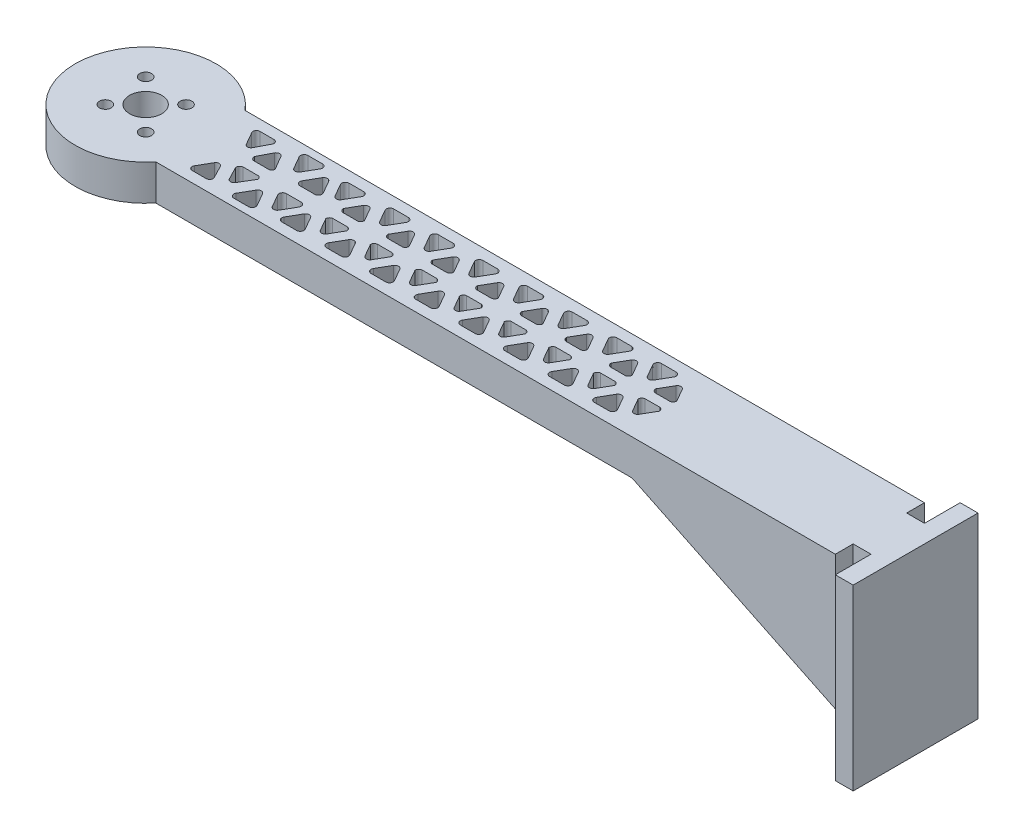
SolidWorks part; units mm, degrees
note: The reader was unsure of these and kept them because the rebuilt part matched: shared geometry of "Sketch2<4>".
ref_plane "Front Plane" through (0, 0, 0) normal (0, 0, 1) x (1, 0, 0)
ref_plane "Top Plane" through (0, 0, 0) normal (0, 1, 0) x (1, 0, 0)
ref_plane "Right Plane" through (0, 0, 0) normal (1, 0, 0) x (0, 0, -1)
sketch "Sketch1" plane through (0, 0, 0) normal (0, 1, 0) x (1, 0, 0)
  line L0 (19.7015, -0.0803) -> (215.7812, -0.0803) construction
  line L1 (15.2517, 12.4197) -> (215.7812, 12.4197)
  line L2 (15.2517, -12.5803) -> (215.7812, -12.5803)
  line L3 (215.7812, 12.4197) -> (215.7812, -12.5803)
  line L4 (22.4549, 9.4197) -> (26.384, 9.4197)
  line L5 (27.2449, 8.0014) -> (25.383, 4.4231)
  line L6 (23.682, 4.3855) -> (21.6147, 7.9638)
  line L7 (29.7182, 6.2554) -> (27.8031, 2.5747)
  line L8 (33.7755, 2.3958) -> (31.5736, 6.0947)
  line L9 (28.7602, 1.4197) -> (33.171, 1.4197)
  line L10 (37.9612, 5.1841) -> (40.0285, 8.7624)
  line L11 (34.1207, 8.7624) -> (36.188, 5.1841)
  line L12 (39.1419, 10.2986) -> (35.0073, 10.2986)
  line L13 (45.3949, 1.819) -> (41.2604, 1.819)
  line L14 (40.3733, 3.3543) -> (42.441, 6.9413)
  line L15 (44.2142, 6.9413) -> (46.2815, 3.363)
  line L16 (47.5213, 9.3393) -> (51.6558, 9.3393)
  line L17 (52.5425, 7.8032) -> (50.4752, 4.2249)
  line L18 (48.702, 4.2249) -> (46.6347, 7.8032)
  line L19 (54.955, 5.982) -> (52.8877, 2.4037)
  line L20 (58.7955, 2.3958) -> (56.7282, 5.982)
  line L21 (53.7743, 1.3393) -> (57.9089, 1.3393)
  line L22 (60.0313, 9.3393) -> (64.1658, 9.3393)
  line L23 (65.0525, 7.8032) -> (62.9852, 4.2249)
  line L24 (61.212, 4.2249) -> (59.1447, 7.8032)
  line L25 (67.465, 5.982) -> (65.3977, 2.4037)
  line L26 (71.3055, 2.3958) -> (69.2382, 5.982)
  line L27 (66.2843, 1.3393) -> (70.4189, 1.3393)
  line L28 (72.5413, 9.3393) -> (76.6758, 9.3393)
  line L29 (77.5625, 7.8032) -> (75.4952, 4.2249)
  line L30 (73.722, 4.2249) -> (71.6547, 7.8032)
  line L31 (79.975, 5.982) -> (77.9077, 2.4037)
  line L32 (83.8155, 2.3958) -> (81.7482, 5.982)
  line L33 (78.7943, 1.3393) -> (82.9289, 1.3393)
  line L34 (85.0513, 9.3393) -> (89.1858, 9.3393)
  line L35 (90.0725, 7.8032) -> (88.0052, 4.2249)
  line L36 (86.232, 4.2249) -> (84.1647, 7.8032)
  line L37 (92.485, 5.982) -> (90.4177, 2.4037)
  line L38 (96.3255, 2.3958) -> (94.2582, 5.982)
  line L39 (91.3043, 1.3393) -> (95.4389, 1.3393)
  line L40 (91.3043, -1.5) -> (95.4389, -1.5)
  line L41 (96.3255, -2.5565) -> (94.2582, -6.1427)
  line L42 (92.485, -6.1427) -> (90.4177, -2.5644)
  line L43 (86.232, -4.3855) -> (84.1647, -7.9638)
  line L44 (90.0725, -7.9638) -> (88.0052, -4.3855)
  line L45 (85.0513, -9.5) -> (89.1858, -9.5)
  line L46 (78.7943, -1.5) -> (82.9289, -1.5)
  line L47 (83.8155, -2.5565) -> (81.7482, -6.1427)
  line L48 (79.975, -6.1427) -> (77.9077, -2.5644)
  line L49 (73.722, -4.3855) -> (71.6547, -7.9638)
  line L50 (77.5625, -7.9638) -> (75.4952, -4.3855)
  line L51 (72.5413, -9.5) -> (76.6758, -9.5)
  line L52 (66.2843, -1.5) -> (70.4189, -1.5)
  line L53 (71.3055, -2.5565) -> (69.2382, -6.1427)
  line L54 (67.465, -6.1427) -> (65.3977, -2.5644)
  line L55 (61.212, -4.3855) -> (59.1447, -7.9638)
  line L56 (65.0525, -7.9638) -> (62.9852, -4.3855)
  line L57 (60.0313, -9.5) -> (64.1658, -9.5)
  line L58 (53.7743, -1.5) -> (57.9089, -1.5)
  line L59 (58.7955, -2.5565) -> (56.7282, -6.1427)
  line L60 (54.955, -6.1427) -> (52.8877, -2.5644)
  line L61 (48.702, -4.3855) -> (46.6347, -7.9638)
  line L62 (52.5425, -7.9638) -> (50.4752, -4.3855)
  line L63 (47.5213, -9.5) -> (51.6558, -9.5)
  line L64 (44.2142, -7.1019) -> (46.2815, -3.5236)
  line L65 (40.3733, -3.5149) -> (42.441, -7.1019)
  line L66 (45.3949, -1.9796) -> (41.2604, -1.9796)
  line L67 (39.1419, -10.4593) -> (35.0073, -10.4593)
  line L68 (34.1207, -8.9231) -> (36.188, -5.3448)
  line L69 (37.9612, -5.3448) -> (40.0285, -8.9231)
  line L70 (28.7602, -1.5803) -> (33.171, -1.5803)
  line L71 (33.7755, -2.5565) -> (31.5736, -6.2554)
  line L72 (29.7182, -6.4161) -> (27.8031, -2.7354)
  line L73 (23.682, -4.5462) -> (21.6147, -8.1245)
  line L74 (27.2449, -8.1621) -> (25.383, -4.5837)
  line L75 (22.4549, -9.5803) -> (26.384, -9.5803)
  line L76 (-0.0803, -16.7095) -> (-0.0803, 16.5488) construction
  line L77 (11.7312, -11.8919) -> (-11.8919, 11.7312) construction
  line L78 (-12.5321, -12.5321) -> (12.3715, 12.3715) construction
  line L79 (97.5613, 9.3393) -> (101.6958, 9.3393)
  line L80 (102.5825, 7.8032) -> (100.5152, 4.2249)
  line L81 (98.742, 4.2249) -> (96.6747, 7.8032)
  line L82 (104.995, 5.982) -> (102.9277, 2.4037)
  line L83 (108.8355, 2.3958) -> (106.7682, 5.982)
  line L84 (103.8143, 1.3393) -> (107.9489, 1.3393)
  line L85 (110.0713, 9.3393) -> (114.2058, 9.3393)
  line L86 (115.0925, 7.8032) -> (113.0252, 4.2249)
  line L87 (111.252, 4.2249) -> (109.1847, 7.8032)
  line L88 (117.505, 5.982) -> (115.4377, 2.4037)
  line L89 (121.3455, 2.3958) -> (119.2782, 5.982)
  line L90 (116.3243, 1.3393) -> (120.4589, 1.3393)
  line L91 (122.5813, 9.3393) -> (126.7158, 9.3393)
  line L92 (127.6025, 7.8032) -> (125.5352, 4.2249)
  line L93 (123.762, 4.2249) -> (121.6947, 7.8032)
  line L94 (130.015, 5.982) -> (127.9477, 2.4037)
  line L95 (133.8555, 2.3958) -> (131.7882, 5.982)
  line L96 (128.8343, 1.3393) -> (132.9689, 1.3393)
  line L97 (135.0913, 9.3393) -> (139.2258, 9.3393)
  line L98 (140.1125, 7.8032) -> (138.0452, 4.2249)
  line L99 (136.272, 4.2249) -> (134.2047, 7.8032)
  line L100 (142.525, 5.982) -> (140.4577, 2.4037)
  line L101 (146.3655, 2.3958) -> (144.2982, 5.982)
  line L102 (141.3443, 1.3393) -> (145.4789, 1.3393)
  line L139 (141.3443, -1.5) -> (145.4789, -1.5)
  line L140 (146.3655, -2.5565) -> (144.2982, -6.1427)
  line L141 (142.525, -6.1427) -> (140.4577, -2.5644)
  line L142 (136.272, -4.3855) -> (134.2047, -7.9638)
  line L143 (140.1125, -7.9638) -> (138.0452, -4.3855)
  line L144 (135.0913, -9.5) -> (139.2258, -9.5)
  line L145 (128.8343, -1.5) -> (132.9689, -1.5)
  line L146 (133.8555, -2.5565) -> (131.7882, -6.1427)
  line L147 (130.015, -6.1427) -> (127.9477, -2.5644)
  line L148 (123.762, -4.3855) -> (121.6947, -7.9638)
  line L149 (127.6025, -7.9638) -> (125.5352, -4.3855)
  line L150 (122.5813, -9.5) -> (126.7158, -9.5)
  line L151 (116.3243, -1.5) -> (120.4589, -1.5)
  line L152 (121.3455, -2.5565) -> (119.2782, -6.1427)
  line L153 (117.505, -6.1427) -> (115.4377, -2.5644)
  line L154 (111.252, -4.3855) -> (109.1847, -7.9638)
  line L155 (115.0925, -7.9638) -> (113.0252, -4.3855)
  line L156 (110.0713, -9.5) -> (114.2058, -9.5)
  line L157 (103.8143, -1.5) -> (107.9489, -1.5)
  line L158 (108.8355, -2.5565) -> (106.7682, -6.1427)
  line L159 (104.995, -6.1427) -> (102.9277, -2.5644)
  line L160 (98.742, -4.3855) -> (96.6747, -7.9638)
  line L161 (102.5825, -7.9638) -> (100.5152, -4.3855)
  line L162 (97.5613, -9.5) -> (101.6958, -9.5)
  line L163 (147.6013, 9.3393) -> (151.7358, 9.3393) [skipped]
  line L164 (152.6225, 7.8032) -> (150.5552, 4.2249) [skipped]
  line L165 (148.782, 4.2249) -> (146.7147, 7.8032) [skipped]
  line L166 (155.035, 5.982) -> (152.9677, 2.4037) [skipped]
  line L167 (158.8755, 2.3958) -> (156.8082, 5.982) [skipped]
  line L168 (153.8543, 1.3393) -> (157.9889, 1.3393) [skipped]
  line L169 (160.1113, 9.3393) -> (164.2458, 9.3393) [skipped]
  line L170 (165.1325, 7.8032) -> (163.0652, 4.2249) [skipped]
  line L171 (161.292, 4.2249) -> (159.2247, 7.8032) [skipped]
  line L172 (167.545, 5.982) -> (165.4777, 2.4037) [skipped]
  line L173 (171.3855, 2.3958) -> (169.3182, 5.982) [skipped]
  line L174 (166.3643, 1.3393) -> (170.4989, 1.3393) [skipped]
  line L175 (172.6213, 9.3393) -> (176.7558, 9.3393) [skipped]
  line L176 (177.6425, 7.8032) -> (175.5752, 4.2249) [skipped]
  line L177 (173.802, 4.2249) -> (171.7347, 7.8032) [skipped]
  line L178 (180.055, 5.982) -> (177.9877, 2.4037) [skipped]
  line L179 (183.8955, 2.3958) -> (181.8282, 5.982) [skipped]
  line L180 (178.8743, 1.3393) -> (183.0089, 1.3393) [skipped]
  circle A0 centre (-0.0803, -0.0803) radius 19.7818
  arc A1 (25.383, 4.4231) -> (23.682, 4.3855) centre (24.5222, 4.871) cw
  arc A2 (22.4549, 9.4197) -> (21.6147, 7.9638) centre (22.4549, 8.4493) ccw
  arc A3 (26.384, 9.4197) -> (27.2449, 8.0014) centre (26.384, 8.4493) cw
  arc A4 (33.171, 1.4197) -> (33.7755, 2.3958) centre (32.7524, 2.3541) ccw
  arc A5 (31.5736, 6.0947) -> (29.7182, 6.2554) centre (30.6092, 5.7508) ccw
  arc A6 (28.7602, 1.4197) -> (27.8031, 2.5747) centre (28.8569, 2.4738) cw
  arc A7 (35.0073, 10.2986) -> (34.1207, 8.7624) centre (35.0073, 9.2747) ccw
  arc A8 (39.1419, 10.2986) -> (40.0285, 8.7624) centre (39.1419, 9.2747) cw
  arc A9 (36.188, 5.1841) -> (37.9612, 5.1841) centre (37.0746, 5.6963) ccw
  arc A10 (45.3949, 1.819) -> (46.2815, 3.363) centre (45.3995, 2.8429) ccw
  arc A11 (42.441, 6.9413) -> (44.2142, 6.9413) centre (43.3276, 6.4291) cw
  arc A12 (41.2604, 1.819) -> (40.3733, 3.3543) centre (41.2604, 2.8429) cw
  arc A13 (50.4752, 4.2249) -> (48.702, 4.2249) centre (49.5886, 4.7371) cw
  arc A14 (47.5213, 9.3393) -> (46.6347, 7.8032) centre (47.5213, 8.3154) ccw
  arc A15 (51.6558, 9.3393) -> (52.5425, 7.8032) centre (51.6558, 8.3154) cw
  arc A16 (57.9089, 1.3393) -> (58.7955, 2.3958) centre (57.7724, 2.3541) ccw
  arc A17 (56.7282, 5.982) -> (54.955, 5.982) centre (55.8416, 5.4698) ccw
  arc A18 (53.7743, 1.3393) -> (52.8877, 2.4037) centre (53.9105, 2.3542) cw
  arc A19 (62.9852, 4.2249) -> (61.212, 4.2249) centre (62.0986, 4.7371) cw
  arc A20 (60.0313, 9.3393) -> (59.1447, 7.8032) centre (60.0313, 8.3154) ccw
  arc A21 (64.1658, 9.3393) -> (65.0525, 7.8032) centre (64.1658, 8.3154) cw
  arc A22 (70.4189, 1.3393) -> (71.3055, 2.3958) centre (70.2824, 2.3541) ccw
  arc A23 (69.2382, 5.982) -> (67.465, 5.982) centre (68.3516, 5.4698) ccw
  arc A24 (66.2843, 1.3393) -> (65.3977, 2.4037) centre (66.4205, 2.3542) cw
  arc A25 (75.4952, 4.2249) -> (73.722, 4.2249) centre (74.6086, 4.7371) cw
  arc A26 (72.5413, 9.3393) -> (71.6547, 7.8032) centre (72.5413, 8.3154) ccw
  arc A27 (76.6758, 9.3393) -> (77.5625, 7.8032) centre (76.6758, 8.3154) cw
  arc A28 (82.9289, 1.3393) -> (83.8155, 2.3958) centre (82.7924, 2.3541) ccw
  arc A29 (81.7482, 5.982) -> (79.975, 5.982) centre (80.8616, 5.4698) ccw
  arc A30 (78.7943, 1.3393) -> (77.9077, 2.4037) centre (78.9305, 2.3542) cw
  arc A31 (88.0052, 4.2249) -> (86.232, 4.2249) centre (87.1186, 4.7371) cw
  arc A32 (85.0513, 9.3393) -> (84.1647, 7.8032) centre (85.0513, 8.3154) ccw
  arc A33 (89.1858, 9.3393) -> (90.0725, 7.8032) centre (89.1858, 8.3154) cw
  arc A34 (95.4389, 1.3393) -> (96.3255, 2.3958) centre (95.3024, 2.3541) ccw
  arc A35 (94.2582, 5.982) -> (92.485, 5.982) centre (93.3716, 5.4698) ccw
  arc A36 (91.3043, 1.3393) -> (90.4177, 2.4037) centre (91.4405, 2.3542) cw
  arc A37 (91.3043, -1.5) -> (90.4177, -2.5644) centre (91.4405, -2.5148) ccw
  arc A38 (94.2582, -6.1427) -> (92.485, -6.1427) centre (93.3716, -5.6305) cw
  arc A39 (95.4389, -1.5) -> (96.3255, -2.5565) centre (95.3024, -2.5148) cw
  arc A40 (89.1858, -9.5) -> (90.0725, -7.9638) centre (89.1858, -8.4761) ccw
  arc A41 (85.0513, -9.5) -> (84.1647, -7.9638) centre (85.0513, -8.4761) cw
  arc A42 (88.0052, -4.3855) -> (86.232, -4.3855) centre (87.1186, -4.8978) ccw
  arc A43 (78.7943, -1.5) -> (77.9077, -2.5644) centre (78.9305, -2.5148) ccw
  arc A44 (81.7482, -6.1427) -> (79.975, -6.1427) centre (80.8616, -5.6305) cw
  arc A45 (82.9289, -1.5) -> (83.8155, -2.5565) centre (82.7924, -2.5148) cw
  arc A46 (76.6758, -9.5) -> (77.5625, -7.9638) centre (76.6758, -8.4761) ccw
  arc A47 (72.5413, -9.5) -> (71.6547, -7.9638) centre (72.5413, -8.4761) cw
  arc A48 (75.4952, -4.3855) -> (73.722, -4.3855) centre (74.6086, -4.8978) ccw
  arc A49 (66.2843, -1.5) -> (65.3977, -2.5644) centre (66.4205, -2.5148) ccw
  arc A50 (69.2382, -6.1427) -> (67.465, -6.1427) centre (68.3516, -5.6305) cw
  arc A51 (70.4189, -1.5) -> (71.3055, -2.5565) centre (70.2824, -2.5148) cw
  arc A52 (64.1658, -9.5) -> (65.0525, -7.9638) centre (64.1658, -8.4761) ccw
  arc A53 (60.0313, -9.5) -> (59.1447, -7.9638) centre (60.0313, -8.4761) cw
  arc A54 (62.9852, -4.3855) -> (61.212, -4.3855) centre (62.0986, -4.8978) ccw
  arc A55 (53.7743, -1.5) -> (52.8877, -2.5644) centre (53.9105, -2.5148) ccw
  arc A56 (56.7282, -6.1427) -> (54.955, -6.1427) centre (55.8416, -5.6305) cw
  arc A57 (57.9089, -1.5) -> (58.7955, -2.5565) centre (57.7724, -2.5148) cw
  arc A58 (51.6558, -9.5) -> (52.5425, -7.9638) centre (51.6558, -8.4761) ccw
  arc A59 (47.5213, -9.5) -> (46.6347, -7.9638) centre (47.5213, -8.4761) cw
  arc A60 (50.4752, -4.3855) -> (48.702, -4.3855) centre (49.5886, -4.8978) ccw
  arc A61 (41.2604, -1.9796) -> (40.3733, -3.5149) centre (41.2604, -3.0036) ccw
  arc A62 (42.441, -7.1019) -> (44.2142, -7.1019) centre (43.3276, -6.5897) ccw
  arc A63 (45.3949, -1.9796) -> (46.2815, -3.5236) centre (45.3995, -3.0036) cw
  arc A64 (36.188, -5.3448) -> (37.9612, -5.3448) centre (37.0746, -5.857) cw
  arc A65 (39.1419, -10.4593) -> (40.0285, -8.9231) centre (39.1419, -9.4353) ccw
  arc A66 (35.0073, -10.4593) -> (34.1207, -8.9231) centre (35.0073, -9.4353) cw
  arc A67 (28.7602, -1.5803) -> (27.8031, -2.7354) centre (28.8569, -2.6345) ccw
  arc A68 (31.5736, -6.2554) -> (29.7182, -6.4161) centre (30.6092, -5.9115) cw
  arc A69 (33.171, -1.5803) -> (33.7755, -2.5565) centre (32.7524, -2.5148) cw
  arc A70 (26.384, -9.5803) -> (27.2449, -8.1621) centre (26.384, -8.61) ccw
  arc A71 (22.4549, -9.5803) -> (21.6147, -8.1245) centre (22.4549, -8.61) cw
  arc A72 (25.383, -4.5837) -> (23.682, -4.5462) centre (24.5222, -5.0316) ccw
  circle A73 centre (-6.7979, 6.6372) radius 1.65
  circle A74 centre (5.5765, 5.5765) radius 1.65
  circle A75 centre (6.6372, -6.7979) radius 1.65
  circle A76 centre (-5.7372, -5.7372) radius 1.65
  circle A77 centre (-0.0803, -0.0803) radius 4.5
  arc A78 (100.5152, 4.2249) -> (98.742, 4.2249) centre (99.6286, 4.7371) cw
  arc A79 (97.5613, 9.3393) -> (96.6747, 7.8032) centre (97.5613, 8.3154) ccw
  arc A80 (101.6958, 9.3393) -> (102.5825, 7.8032) centre (101.6958, 8.3154) cw
  arc A81 (107.9489, 1.3393) -> (108.8355, 2.3958) centre (107.8124, 2.3541) ccw
  arc A82 (106.7682, 5.982) -> (104.995, 5.982) centre (105.8816, 5.4698) ccw
  arc A83 (103.8143, 1.3393) -> (102.9277, 2.4037) centre (103.9505, 2.3542) cw
  arc A84 (113.0252, 4.2249) -> (111.252, 4.2249) centre (112.1386, 4.7371) cw
  arc A85 (110.0713, 9.3393) -> (109.1847, 7.8032) centre (110.0713, 8.3154) ccw
  arc A86 (114.2058, 9.3393) -> (115.0925, 7.8032) centre (114.2058, 8.3154) cw
  arc A87 (120.4589, 1.3393) -> (121.3455, 2.3958) centre (120.3224, 2.3541) ccw
  arc A88 (119.2782, 5.982) -> (117.505, 5.982) centre (118.3916, 5.4698) ccw
  arc A89 (116.3243, 1.3393) -> (115.4377, 2.4037) centre (116.4605, 2.3542) cw
  arc A90 (125.5352, 4.2249) -> (123.762, 4.2249) centre (124.6486, 4.7371) cw
  arc A91 (122.5813, 9.3393) -> (121.6947, 7.8032) centre (122.5813, 8.3154) ccw
  arc A92 (126.7158, 9.3393) -> (127.6025, 7.8032) centre (126.7158, 8.3154) cw
  arc A93 (132.9689, 1.3393) -> (133.8555, 2.3958) centre (132.8324, 2.3541) ccw
  arc A94 (131.7882, 5.982) -> (130.015, 5.982) centre (130.9016, 5.4698) ccw
  arc A95 (128.8343, 1.3393) -> (127.9477, 2.4037) centre (128.9705, 2.3542) cw
  arc A96 (138.0452, 4.2249) -> (136.272, 4.2249) centre (137.1586, 4.7371) cw
  arc A97 (135.0913, 9.3393) -> (134.2047, 7.8032) centre (135.0913, 8.3154) ccw
  arc A98 (139.2258, 9.3393) -> (140.1125, 7.8032) centre (139.2258, 8.3154) cw
  arc A99 (145.4789, 1.3393) -> (146.3655, 2.3958) centre (145.3424, 2.3541) ccw
  arc A100 (144.2982, 5.982) -> (142.525, 5.982) centre (143.4116, 5.4698) ccw
  arc A101 (141.3443, 1.3393) -> (140.4577, 2.4037) centre (141.4805, 2.3542) cw
  arc A138 (141.3443, -1.5) -> (140.4577, -2.5644) centre (141.4805, -2.5148) ccw
  arc A139 (144.2982, -6.1427) -> (142.525, -6.1427) centre (143.4116, -5.6305) cw
  arc A140 (145.4789, -1.5) -> (146.3655, -2.5565) centre (145.3424, -2.5148) cw
  arc A141 (139.2258, -9.5) -> (140.1125, -7.9638) centre (139.2258, -8.4761) ccw
  arc A142 (135.0913, -9.5) -> (134.2047, -7.9638) centre (135.0913, -8.4761) cw
  arc A143 (138.0452, -4.3855) -> (136.272, -4.3855) centre (137.1586, -4.8978) ccw
  arc A144 (128.8343, -1.5) -> (127.9477, -2.5644) centre (128.9705, -2.5148) ccw
  arc A145 (131.7882, -6.1427) -> (130.015, -6.1427) centre (130.9016, -5.6305) cw
  arc A146 (132.9689, -1.5) -> (133.8555, -2.5565) centre (132.8324, -2.5148) cw
  arc A147 (126.7158, -9.5) -> (127.6025, -7.9638) centre (126.7158, -8.4761) ccw
  arc A148 (122.5813, -9.5) -> (121.6947, -7.9638) centre (122.5813, -8.4761) cw
  arc A149 (125.5352, -4.3855) -> (123.762, -4.3855) centre (124.6486, -4.8978) ccw
  arc A150 (116.3243, -1.5) -> (115.4377, -2.5644) centre (116.4605, -2.5148) ccw
  arc A151 (119.2782, -6.1427) -> (117.505, -6.1427) centre (118.3916, -5.6305) cw
  arc A152 (120.4589, -1.5) -> (121.3455, -2.5565) centre (120.3224, -2.5148) cw
  arc A153 (114.2058, -9.5) -> (115.0925, -7.9638) centre (114.2058, -8.4761) ccw
  arc A154 (110.0713, -9.5) -> (109.1847, -7.9638) centre (110.0713, -8.4761) cw
  arc A155 (113.0252, -4.3855) -> (111.252, -4.3855) centre (112.1386, -4.8978) ccw
  arc A156 (103.8143, -1.5) -> (102.9277, -2.5644) centre (103.9505, -2.5148) ccw
  arc A157 (106.7682, -6.1427) -> (104.995, -6.1427) centre (105.8816, -5.6305) cw
  arc A158 (107.9489, -1.5) -> (108.8355, -2.5565) centre (107.8124, -2.5148) cw
  arc A159 (101.6958, -9.5) -> (102.5825, -7.9638) centre (101.6958, -8.4761) ccw
  arc A160 (97.5613, -9.5) -> (96.6747, -7.9638) centre (97.5613, -8.4761) cw
  arc A161 (100.5152, -4.3855) -> (98.742, -4.3855) centre (99.6286, -4.8978) ccw
  arc A162 (150.5552, 4.2249) -> (148.782, 4.2249) centre (149.6686, 4.7371) cw [skipped]
  arc A163 (147.6013, 9.3393) -> (146.7147, 7.8032) centre (147.6013, 8.3154) ccw [skipped]
  arc A164 (151.7358, 9.3393) -> (152.6225, 7.8032) centre (151.7358, 8.3154) cw [skipped]
  arc A165 (157.9889, 1.3393) -> (158.8755, 2.3958) centre (157.8524, 2.3541) ccw [skipped]
  arc A166 (156.8082, 5.982) -> (155.035, 5.982) centre (155.9216, 5.4698) ccw [skipped]
  arc A167 (153.8543, 1.3393) -> (152.9677, 2.4037) centre (153.9905, 2.3542) cw [skipped]
  arc A168 (163.0652, 4.2249) -> (161.292, 4.2249) centre (162.1786, 4.7371) cw [skipped]
  arc A169 (160.1113, 9.3393) -> (159.2247, 7.8032) centre (160.1113, 8.3154) ccw [skipped]
  arc A170 (164.2458, 9.3393) -> (165.1325, 7.8032) centre (164.2458, 8.3154) cw [skipped]
  arc A171 (170.4989, 1.3393) -> (171.3855, 2.3958) centre (170.3624, 2.3541) ccw [skipped]
  arc A172 (169.3182, 5.982) -> (167.545, 5.982) centre (168.4316, 5.4698) ccw [skipped]
  arc A173 (166.3643, 1.3393) -> (165.4777, 2.4037) centre (166.5005, 2.3542) cw [skipped]
  arc A174 (175.5752, 4.2249) -> (173.802, 4.2249) centre (174.6886, 4.7371) cw [skipped]
  arc A175 (172.6213, 9.3393) -> (171.7347, 7.8032) centre (172.6213, 8.3154) ccw [skipped]
  arc A176 (176.7558, 9.3393) -> (177.6425, 7.8032) centre (176.7558, 8.3154) cw [skipped]
  arc A177 (183.0089, 1.3393) -> (183.8955, 2.3958) centre (182.8724, 2.3541) ccw [skipped]
  arc A178 (181.8282, 5.982) -> (180.055, 5.982) centre (180.9416, 5.4698) ccw [skipped]
  arc A179 (178.8743, 1.3393) -> (177.9877, 2.4037) centre (179.0105, 2.3542) cw [skipped]
  point P5 (-0.0803, -0.0803)
  point P8 (-0.0803, -0.0803)
  point P55 (30.6092, 5.7508)
  point P66 (37.0746, 5.6963)
  point P74 (43.3276, 6.4291)
  point P93 (55.8416, 5.4698)
  point P112 (68.3516, 5.4698)
  point P131 (80.8616, 5.4698)
  point P150 (93.3716, 5.4698)
  point P239 (93.3716, -5.6305)
  point P240 (80.8616, -5.6305)
  point P241 (68.3516, -5.6305)
  point P242 (55.8416, -5.6305)
  point P243 (43.3276, -6.5897)
  point P244 (37.0746, -5.857)
  point P245 (30.6092, -5.9115)
  point P247 (-0.0803, -0.0803)
  point P256 (180.9416, 5.4698)
  point P257 (168.4316, 5.4698)
  point P276 (105.8816, 5.4698)
  point P295 (118.3916, 5.4698)
  point P314 (130.9016, 5.4698)
  point P333 (143.4116, 5.4698)
  point P334 (155.9216, 5.4698)
  point P518 (143.4116, -5.6305)
  point P519 (130.9016, -5.6305)
  point P520 (118.3916, -5.6305)
  point P521 (105.8816, -5.6305)
  dimension "D7" = 3.3
  dimension "D8" = 3.3
  dimension "D9" = 3.3
  dimension "D10" = 3.3
  dimension "D15" = 9
  dimension "D1" = 3
  dimension "D2" = 3
  dimension "D3" = 25
  dimension "D4" = 3
  dimension "D5" = 45
  dimension "D6" = 90
  dimension "D11" = 9.5
  dimension "D12" = 9.5
  dimension "D13" = 8
  dimension "D14" = 8
  dimension "D16" = 8
extrude "Boss-Extrude1" add sketch "Sketch1" along normal blind 10
sketch "Sketch2" plane through (0, 10, 0) normal (0, 1, 0) x (1, 0, 0)
  line L0 (215.7812, 12.4197) -> (215.7812, 17.4197)
  line L1 (215.7812, 17.4197) -> (210.7812, 17.4197)
  line L2 (210.7812, 17.4197) -> (210.7812, -12.5803)
  line L3 (15.2517, -12.5803) -> (215.7812, -12.5803) construction
  line L4 (210.7812, -12.5803) -> (210.7812, -17.5803)
  line L5 (210.7812, -17.5803) -> (215.7812, -17.5803)
  line L6 (215.7812, -17.5803) -> (215.7812, -12.5803)
  line L7 (215.7812, -12.5803) -> (215.7812, 12.4197)
  line L8 (210.7812, -12.5803) -> (205.7812, -12.5803)
  line L17 (205.7812, -12.5803) -> (205.7812, -7.5803)
  line L18 (205.7812, -7.5803) -> (210.7812, -7.5803)
  line L19 (205.7812, 12.4197) -> (205.7812, 7.4197)
  line L20 (15.2517, 12.4197) -> (215.7812, 12.4197) construction
  line L21 (205.7812, 7.4197) -> (210.7812, 7.4197)
  line L22 (205.7812, 12.4197) -> (210.7812, 12.4197)
  line L23 (210.7812, 12.4197) -> (210.7812, 7.4197)
  line L24 (210.7812, -7.5803) -> (210.7812, -12.5803)
  dimension "D1" = 5
  dimension "D2" = 5
  dimension "D3" = 5
  dimension "D4" = 5
  dimension "D5" = 5
  dimension "D6" = 5
extrude "Boss-Extrude2" add sketch "Sketch2" against normal blind 50 contours L6 L7 L0 L1 L2 L4 L5
sketch "Sketch3" plane through (0, 0, 12.5803) normal (0, 0, 1) x (1, 0, 0)
  line L8 (210.7812, 0) -> (148.7812, 0)
  line L9 (15.2517, 0) -> (210.7812, 0) construction
  line L10 (210.7812, 0) -> (210.7812, -30)
  line L11 (210.7812, -40) -> (210.7812, 10) construction
  line L12 (210.7812, -30) -> (148.7812, 0)
extrude "Boss-Extrude3" add sketch "Sketch3" against normal up to surface (25 mm away) up to face at (113.0165, 5, -12.4197)
extrude "Cut-Extrude1" cut sketch "Sketch2<4>" against normal up to surface (40 mm away) contours L22 L19 L21 L2 | L18 L17 L8 L2
sketch "Sketch2<4>" plane through (0, 10, 0) normal (0, 1, 0) x (1, 0, 0) same geometry as "Sketch2"
